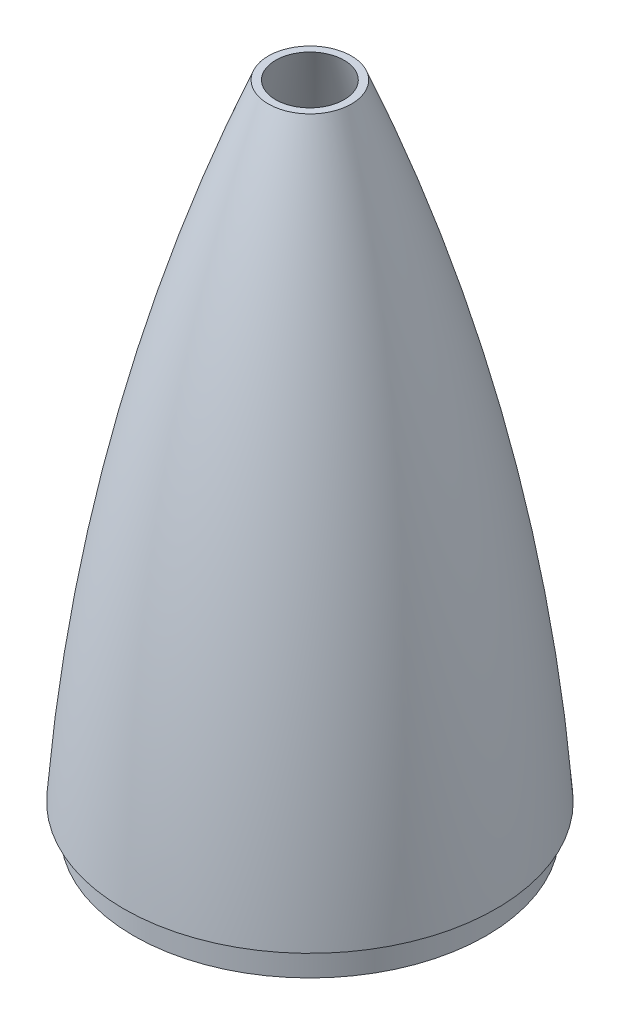
SolidWorks part; units mm, degrees
material "PVB"
ref_plane "Front Plane" through (0, 0, 0) normal (0, 0, 1) x (1, 0, 0)
ref_plane "Top Plane" through (0, 0, 0) normal (0, 1, 0) x (1, 0, 0)
ref_plane "Right Plane" through (0, 0, 0) normal (1, 0, 0) x (0, 0, -1)
sketch "Sketch2" plane through (0, 0, 0) normal (0, 0, 1) x (1, 0, 0)
  line L0 (0, 0) -> (0, 381) construction
  line L1 (-98.425, 0) -> (-90.551, 0)
  line L2 (0, 381) -> (0, 375.92)
  arc A0 (0, 381) -> (-98.425, 0) centre (992.1135, -78.5092) ccw
  arc A1 (0, 375.92) -> (-90.551, 0) centre (1112.691, -90.9691) ccw
  dimension "D1" = 381
  dimension "D2" = 5.08
  dimension "D3" = 98.425
  dimension "D4" = 7.874
revolve "Revolve1" add sketch "Sketch2" angle 360 about L2
sketch "Sketch3" plane through (0, 0, 0) normal (0, -1, 0) x (1, 0, 0)
  circle A0 centre (0, 0) radius 88.9
  circle A1 centre (0, 0) radius 86.995
  dimension "D1" = 177.8
extrude "Boss-Extrude1" [suppressed] add sketch "Sketch3" along normal blind 35.56
sketch "Sketch4" plane through (0, 0, 0) normal (0, -1, 0) x (-1, 0, 0)
  circle A0 centre (0, 0) radius 93.1545
  circle A1 centre (0, 0) radius 90.4875
  dimension "D1" = 186.309
  dimension "D2" = 180.975
extrude "Boss-Extrude2" add sketch "Sketch4" along normal blind 15
ref_plane "Plane1" through (0, 7.86, 0) normal (0, -1, 0) x (-1, 0, 0)
sketch "Sketch6" plane through (0, 7.86, 0) normal (0, -1, 0) x (-1, 0, 0)
  circle A0 centre (0, 0) radius 221.0288
extrude "Cut-Extrude1" [suppressed] cut sketch "Sketch6" against normal blind 457.2
ref_plane "Plane2" through (0, 381, 0) normal (0, 1, 0) x (1, 0, 0)
sketch "Sketch7" plane through (0, 381, 0) normal (0, 1, 0) x (1, 0, 0)
  circle A0 centre (0, 0) radius 317.5
  dimension "D1" = 635
extrude "Cut-Extrude2" cut sketch "Sketch7" against normal blind 50.8
